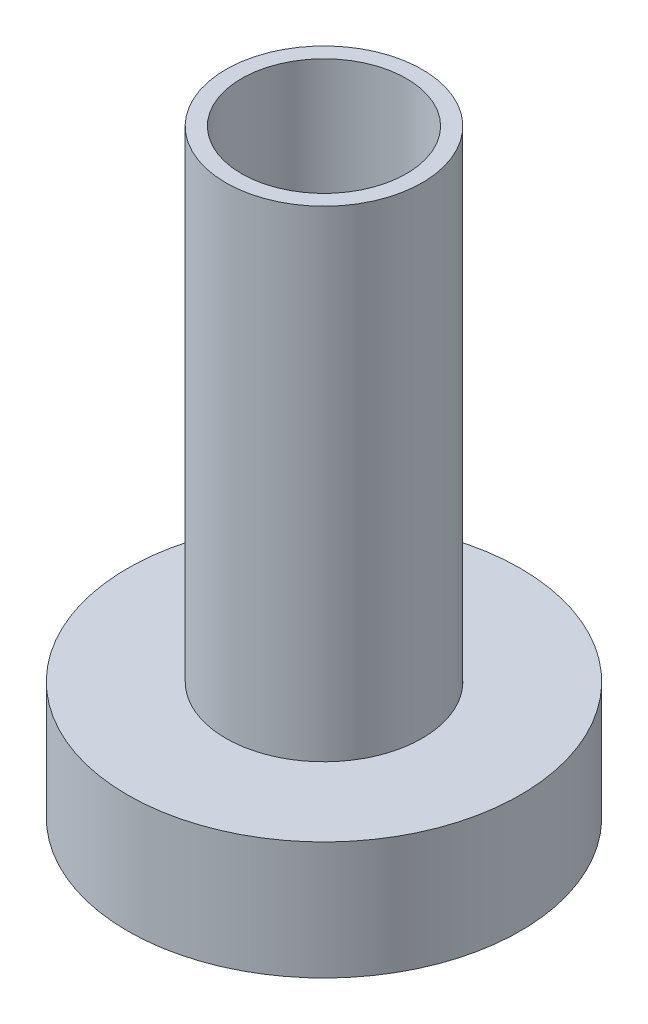
SolidWorks part; units mm, degrees
ref_plane "Plano frontal" through (0, 0, 0) normal (0, 0, 1) x (1, 0, 0)
ref_plane "Plano superior" through (0, 0, 0) normal (0, 1, 0) x (1, 0, 0)
ref_plane "Plano direito" through (0, 0, 0) normal (1, 0, 0) x (0, 0, -1)
sketch "Esboço1" plane through (0, 0, 0) normal (0, 1, 0) x (1, 0, 0)
  circle A0 centre (0, 0) radius 21
  circle A1 centre (0, 0) radius 7
  circle A2 centre (0, 0) radius 25
  dimension "D1" = 42
  dimension "D2" = 14
  dimension "D3" = 50
extrude "Ressalto-extrusão1" add sketch "Esboço1" along normal blind 142.5 contours A2 A0 region at (-24.2929, 0, 0)
extrude "Ressalto-extrusão2" add sketch "Esboço1<4>" against normal blind 10 separate body contours A0 A1 | A2 A0 region at (-20.406, 0, 0) region at (-24.2929, 0, 0)
sketch "Esboço1<4>" plane through (0, 0, 0) normal (0, 1, 0) x (1, 0, 0) same geometry as "Esboço1"
sketch "Esboço2" plane through (0, -10, 0) normal (0, -1, 0) x (1, 0, 0)
  circle A0 centre (0, 0) radius 50
  circle A1 centre (0, 0) radius 25
  dimension "D1" = 100
  dimension "D2" = 50
extrude "Ressalto-extrusão3" add sketch "Esboço2" against normal blind 30 separate body
combine bodies "Combinar1" operation type add bodies to combine 102 103
